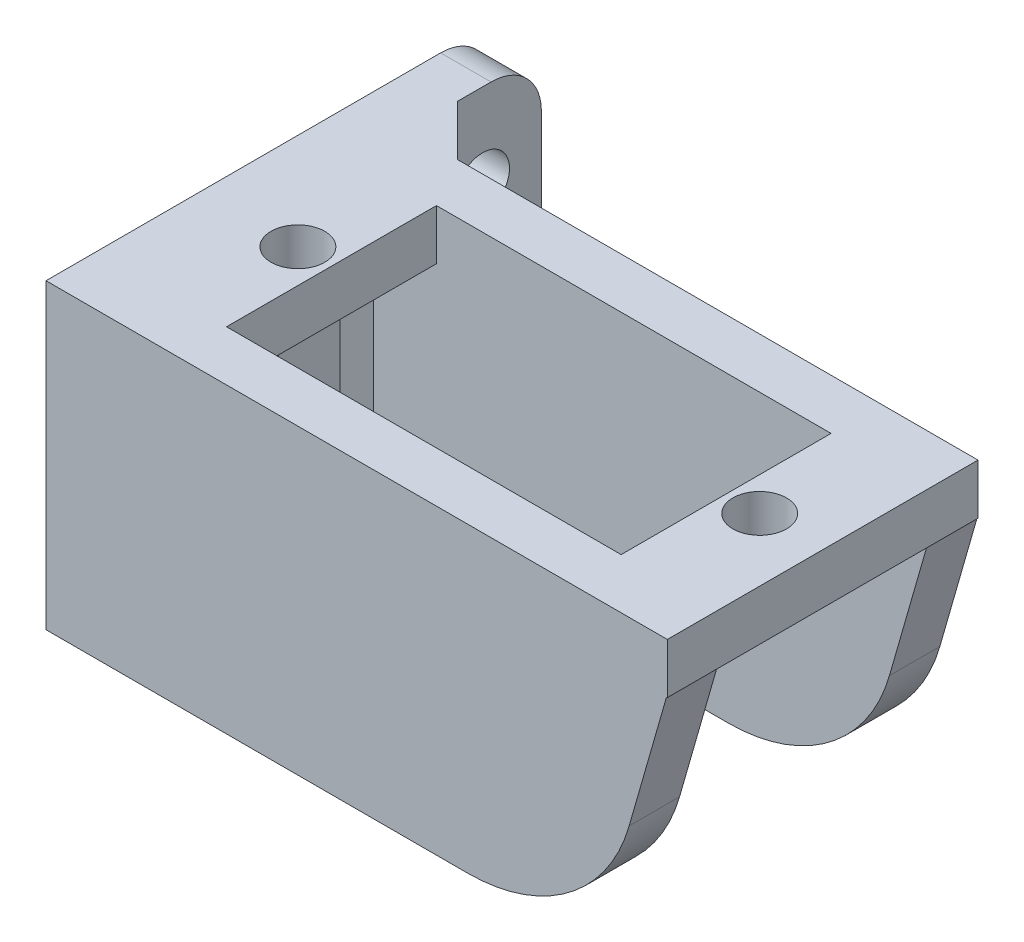
SolidWorks part; units mm, degrees
ref_plane "前视基准面" through (0, 0, 0) normal (0, 0, 1) x (1, 0, 0)
ref_plane "上视基准面" through (0, 0, 0) normal (0, 1, 0) x (1, 0, 0)
ref_plane "右视基准面" through (0, 0, 0) normal (1, 0, 0) x (0, 0, -1)
other "Configuration Table"
sketch "草图1" plane through (0, 0, 0) normal (0, 1, 0) x (1, 0, 0)
  line L1 (0, 0) -> (35, 0)
  line L2 (0, 0) -> (0, 18.5)
  line L3 (0, 18.5) -> (35, 18.5)
  line L4 (35, 0) -> (35, 18.5)
  dimension "D1" = 35
  dimension "D2" = 18.5
extrude "凸台-拉伸1" add sketch "草图1" along normal blind 3
sketch "草图2" plane through (0, 3, 0) normal (0, 1, 0) x (1, 0, 0)
  line L0 (0, 18.5) -> (0, 0) construction
  line L1 (5.75, 15.5) -> (29.25, 15.5)
  line L2 (5.75, 15.5) -> (5.75, 3)
  line L3 (5.75, 3) -> (29.25, 3)
  line L4 (29.25, 15.5) -> (29.25, 3)
  line L5 (35, 18.5) -> (0, 18.5) construction
  line L6 (35, 0) -> (35, 18.5) construction
  circle A0 centre (3.75, 9.25) radius 1.6
  circle A1 centre (31.25, 9.25) radius 1.6
  point P4 (5.75, 9.25)
  point P7 (0, 9.25)
  point P8 (17.5, 15.5)
  point P11 (17.5, 18.5)
  point P18 (35, 9.25)
  dimension "D5" = 13.75
  dimension "D6" = 13.75
  dimension "D7" = 3.2
  dimension "D8" = 3.2
  dimension "D9" = 0
  dimension "D10" = 0
  dimension "D1" = 23.5
  dimension "D2" = 12.5
  dimension "D3" = 0
  dimension "D4" = 0
extrude "切除-拉伸1" cut sketch "草图2" against normal through all
sketch "草图3" plane through (0, 3, 0) normal (0, 1, 0) x (1, 0, 0)
  line L0 (35, 18.5) -> (0, 18.5) construction
  line L1 (0, 0) -> (-2, 0)
  line L2 (0, 0) -> (0, 18.5)
  line L3 (0, 18.5) -> (-2, 18.5)
  line L4 (-2, 0) -> (-2, 18.5)
  dimension "D1" = 2
  dimension "D2" = 0
extrude "凸台-拉伸2" add sketch "草图3" against normal blind 3
sketch "草图5" plane through (0, 0, 0) normal (0, -1, 0) x (-1, 0, 0)
  line L0 (2, 18.5) -> (2, 0) construction
  line L1 (-29.25, 15.5) -> (-1, 15.5)
  line L2 (-29.25, 15.5) -> (-29.25, 18.5)
  line L3 (-29.25, 18.5) -> (2, 18.5)
  line L4 (2, 16.25) -> (2, 18.5)
  line L5 (-29.25, 3) -> (-1, 3)
  line L6 (-29.25, 3) -> (-29.25, 0)
  line L7 (-29.25, 0) -> (2, 0)
  line L8 (2, 3.75) -> (2, 0)
  line L11 (2, 16.25) -> (2, 3.75)
  line L13 (-1, 15.5) -> (-1, 3)
  dimension "D1" = 3
  dimension "D2" = 3
  dimension "D3" = 0
  dimension "D4" = 0
  dimension "D5" = 3
extrude "凸台-拉伸3" add sketch "草图5" along normal blind 15
chamfer "倒角1" distance 5.7 angle 74 2 edges at (29.25, 0, -17) (29.25, 0, -1.5) first distance on face at (31.1667, 0, -9.25)
sketch "草图6" plane through (1, 0, 0) normal (1, 0, 0) x (0, 0, -1)
  line L3 (15.5, -15) -> (3, -15) construction
  circle A2 centre (9.25, -4.6) radius 1.6
  circle A3 centre (9.25, -11.4) radius 1.6
  point P3 (9.25, -15)
  dimension "D2" = 3.2
  dimension "D3" = 0
  dimension "D4" = 0
  dimension "D5" = 3.6
  dimension "D6" = 6.8
  dimension "D10" = 3.2
extrude "切除-拉伸2" cut sketch "草图6" against normal through all
sketch "草图8" plane through (0, 0, -18.5) normal (0, 0, -1) x (-1, 0, 0)
  line L0 (2, -15) -> (-30.6488, -15) construction
  line L1 (2, 3) -> (-1, 3)
  line L2 (2, 3) -> (2, -15)
  line L3 (2, -15) -> (-1, -15)
  line L4 (-1, 3) -> (-1, -15)
  dimension "D1" = 3
extrude "凸台-拉伸4" add sketch "草图8" along normal blind 8
chamfer "倒角2" distance 3 angle 45 1 edges at (1, -6, -18.5)
sketch "草图10" plane through (1, 0, 0) normal (1, 0, 0) x (0, 0, -1)
  line L0 (26.5, 3) -> (26.5, -15) construction
  line L1 (26.5, -15) -> (21.5, -15) construction
  line L2 (26.5, 3) -> (21.5, 3) construction
  circle A0 centre (23, -2) radius 1.6
  circle A1 centre (23, -10) radius 1.6
  dimension "D1" = 3.2
  dimension "D2" = 3.2
  dimension "D3" = 3.5
  dimension "D4" = 3.5
  dimension "D5" = 5
  dimension "D6" = 5
extrude "切除-拉伸3" cut sketch "草图10" against normal through all and the other way through all
sketch "草图11" plane through (1, 0, 0) normal (1, 0, 0) x (0, 0, -1)
  circle A0 centre (23, -2) radius 2.5
  circle A1 centre (23, -10) radius 2.5
  dimension "D1" = 5
  dimension "D2" = 5
extrude "切除-拉伸4" cut sketch "草图11" along normal through all
fillet "圆角1" radius 3 2 edges at (-0.5, -15, -26.5) (-0.5, 3, -26.5)
fillet "圆角2" radius 10 2 edges at (30.6488, -15, -17) (30.6488, -15, -1.5)
chamfer "倒角3" distance 1 angle 45 2 edges at (1, -7.5, -15.5) (1, -7.5, -3)
equation "\"D2@草图1\"=20-1.5"
